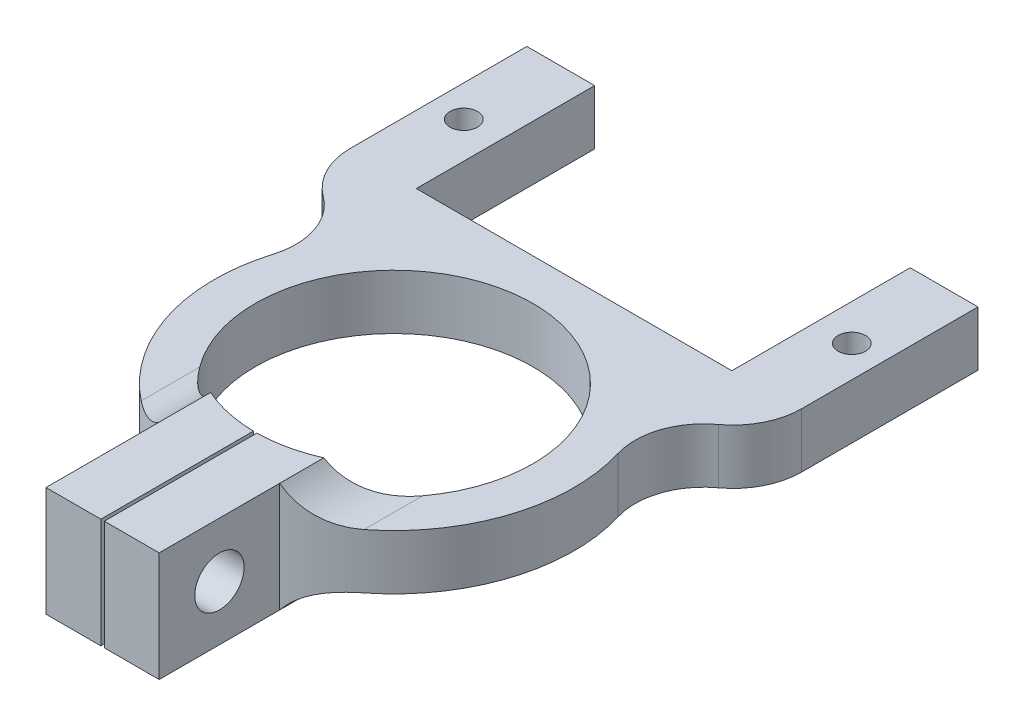
SolidWorks part; units mm, degrees
ref_plane "Front Plane" through (0, 0, 0) normal (0, 0, 1) x (1, 0, 0)
ref_plane "Top Plane" through (0, 0, 0) normal (0, 1, 0) x (1, 0, 0)
ref_plane "Right Plane" through (0, 0, 0) normal (1, 0, 0) x (0, 0, -1)
sketch "Sketch1" plane through (0, 0, 0) normal (0, 1, 0) x (1, 0, 0)
  line L0 (-11.5, 0) -> (11.5, 0)
  line L1 (11.5, 0) -> (11.5, 13)
  line L2 (11.5, 13) -> (16.444, 13)
  line L3 (16.444, 13) -> (16.444, -3)
  line L4 (16.444, -3) -> (-16.444, -3)
  line L5 (-16.444, -3) -> (-16.444, 13)
  line L6 (-16.444, 13) -> (-11.5, 13)
  line L7 (-11.5, 13) -> (-11.5, 0)
  line L8 (0, 0) -> (0, -13.125) construction
  line L13 (0, -13.125) -> (0, -23.25) construction
  line L15 (-0.125, -23.2492) -> (-0.125, -34.3716)
  line L16 (-0.125, -34.3716) -> (-4.125, -34.3716)
  line L17 (-4.125, -22.3716) -> (-4.125, -34.3716)
  line L19 (0.125, -23.2492) -> (0.125, -34.3716)
  line L20 (0.125, -34.3716) -> (4.125, -34.3716)
  line L21 (4.125, -22.3716) -> (4.125, -34.3716)
  line L22 (-0.125, -23.25) -> (0.125, -23.25) construction
  circle A0 centre (0, -13.125) radius 10.125
  circle A1 centre (0, -13.125) radius 13.125
  point P4 (0, 0)
  point P31 (0, -23.25)
  dimension "D1" = 20.25
  dimension "D2" = 3
  dimension "D3" = 23
  dimension "D4" = 13
  dimension "D5" = 0.25
  dimension "D6" = 4
  dimension "D7" = 4
  dimension "D8" = 12
extrude "Boss-Extrude1" add sketch "Sketch1" along normal mid plane 4 contours A1 L4 L3 L2 L1 L0 | A1 L0 L7 L6 L5 L4 | L21 A1 L4 A0 | L4 A1 | L4 A1 L17 A0 | L17 A1 L15 A0 | L19 A1 L21 A0 | A1 L19 L20 L21 | A1 L17 L16 L15 region at (-12.9466, 0, -3.8805) region at (12.9466, 0, -3.8805) region at (0, 0, 1.7874) region at (11.6356, 0, 7.6395) region at (-4.1758, 0, 3.2612) region at (-2.1514, 0, 30.1954) region at (-2.1477, 0, 24.484) region at (2.1477, 0, 24.484) region at (2.1514, 0, 30.1954)
extrude "Boss-Extrude2" add sketch "Sketch1<3>" along normal mid plane 8 contours A1 L19 L20 L21 | A1 L17 L16 L15 | L19 A1 L21 A0 | L17 A1 L15 A0 region at (-2.1514, 0, 30.1954) region at (-2.1477, 0, 24.484) region at (2.1477, 0, 24.484) region at (2.1514, 0, 30.1954)
sketch "Sketch1<3>" plane through (0, 0, 0) normal (0, 1, 0) x (1, 0, 0) same geometry as "Sketch1"
hole_wizard "M3 Clearance Hole1" positions "Sketch2" profile "Sketch3" hole size "M3" standard "ANSI Metric" end condition through all
sketch "Sketch2" plane through (-4.125, 0, 0) normal (-1, 0, 0) x (0, 0, 1)
  line L0 (25.5849, 0) -> (34.3716, 0) construction
  line L1 (25.5849, 2) -> (25.5849, -2) construction
  line L2 (34.3716, 4) -> (34.3716, -4) construction
  point P0 (29.9783, 0)
sketch "Sketch3" plane through (-4.125, 0, 29.9783) normal (0, 1, 0) x (0, 0, 1)
  line L0 (0, 0) -> (0, 20.569)
  line L1 (0, 20.569) -> (1.8, 20.569)
  line L2 (1.8, 20.569) -> (1.8, 0)
  line L5 (1.8, 0) -> (0, 0)
  line L11 (0, -6.35) -> (0, 107.95) construction
  dimension "Thru Hole Dia." = 3.6
  dimension "Thru Hole Depth" = 20.569
fillet "Fillet1" radius 5 6 edges at (-4.125, 2, 23.9783) (4.125, 2, 23.9783) (4.125, -2, 23.9783) (-4.125, -2, 23.9783) (8.3516, 0, 3) (-8.3516, 0, 3)
fillet "Fillet2" radius 5 2 edges at (-16.444, 0, 3) (16.444, 0, 3)
sketch "Sketch4" plane through (0, 2, 0) normal (0, 1, 0) x (1, 0, 0)
  line L0 (-16.444, 0.1469) -> (-16.444, 13) construction
  line L1 (-16.444, 13) -> (-11.5, 13) construction
  line L2 (0, 0) -> (0, 19.8006)
  circle A0 centre (-14.144, 6.1) radius 1
  circle A1 centre (14.144, 6.1) radius 1
  dimension "D3" = 2
  dimension "D1" = 2.3
  dimension "D2" = 6.9
extrude "Cut-Extrude1" cut sketch "Sketch4" against normal blind 10 contours A1 | A0 region at (-14.144, 2, -6.1) region at (14.144, 2, -6.1)
